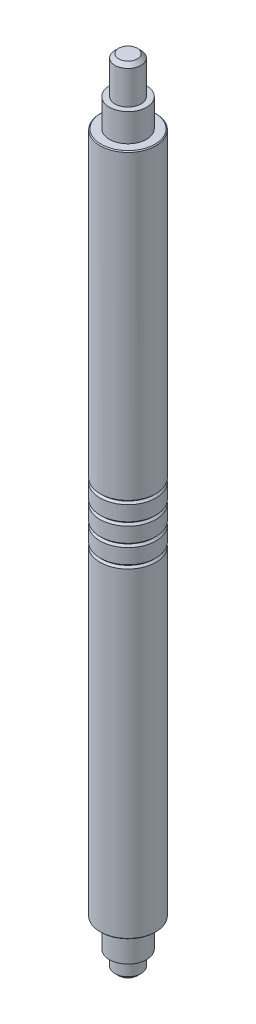
SolidWorks part; units mm, degrees
ref_plane "Front Plane" through (0, 0, 0) normal (0, 0, 1) x (1, 0, 0)
ref_plane "Top Plane" through (0, 0, 0) normal (0, 1, 0) x (1, 0, 0)
ref_plane "Right Plane" through (0, 0, 0) normal (1, 0, 0) x (0, 0, -1)
sketch "Sketch1" plane through (0, 0, 0) normal (0, 1, 0) x (1, 0, 0)
  circle A0 centre (0, 0) radius 1.5
  dimension "D1" = 3
extrude "Boss-Extrude1" add sketch "Sketch1" along normal blind 42.75
sketch "Sketch2" plane through (0, 42.75, 0) normal (0, 1, 0) x (1, 0, 0)
  circle A0 centre (0, 0) radius 1
  dimension "D1" = 2
extrude "Cut-Extrude1" cut sketch "Sketch2" against normal blind 3.5 flip side to cut
sketch "Sketch3" plane through (0, 42.75, 0) normal (0, 1, 0) x (1, 0, 0)
  circle A0 centre (0, 0) radius 0.7
  dimension "D1" = 1.4
extrude "Cut-Extrude2" cut sketch "Sketch3" against normal blind 2 flip side to cut
cosmetic thread "Cosmetic Thread1" parameters "D2"=1.057
sketch "Sketch4" plane through (0, 0, 0) normal (0, -1, 0) x (1, 0, 0)
  circle A0 centre (0, 0) radius 1 construction
  circle A1 centre (0, 0) radius 1
extrude "Cut-Extrude5" cut sketch "Sketch4" against normal offset from surface (2.5 mm away) 36.75 flip side to cut up to face at (0, 39.25, 1)
sketch "Sketch5" plane through (0, 0, 0) normal (0, -1, 0) x (1, 0, 0)
  circle A0 centre (0, 0) radius 0.7 construction
  circle A1 centre (0, 0) radius 0.7
extrude "Cut-Extrude6" cut sketch "Sketch5" against normal offset from surface (1 mm away) 1.5 flip side to cut up to face at (0, 2.5, 1)
cosmetic thread "Cosmetic Thread2" parameters "D2"=1.057
sketch "Sketch6" plane through (0, 0, 0) normal (0, 0, 1) x (1, 0, 0)
  line L0 (0, 42.75) -> (0, 2.7768) construction
  line L1 (0.7, 42.75) -> (-0.7, 42.75) construction
  line L2 (-1.5, 22.975) -> (-1.4, 22.875)
  line L3 (-1.5, 39.25) -> (-1.5, 2.5) construction
  line L4 (-1.4, 22.875) -> (-1.5, 22.775)
  line L5 (-1.4, 22.875) -> (-2.2691, 22.875) construction
  line L6 (1.5, 39.25) -> (-1.5, 39.25) construction
  line L7 (-1.5, 22.975) -> (-1.5, 22.775)
  dimension "D1" = 0.1
  dimension "D2" = 16.375
revolve "Cut-Revolve1" cut sketch "Sketch6" angle 360 about L0
pattern_linear "LPattern1" count 4 spacing 1 along (0, -1, 0) of "Cut-Revolve1"
chamfer "Chamfer3" distance 0.2 angle 45 2 edges at (0, 42.75, 0.7) (0, 0, -0.7)
chamfer "Chamfer4" distance 0.05 angle 45 2 edges at (0, 2.5, 1.5) (0, 39.25, 1.5)
ref_plane "Plane1" through (0, 22.875, 0) normal (0, 1, 0) x (1, 0, 0)
